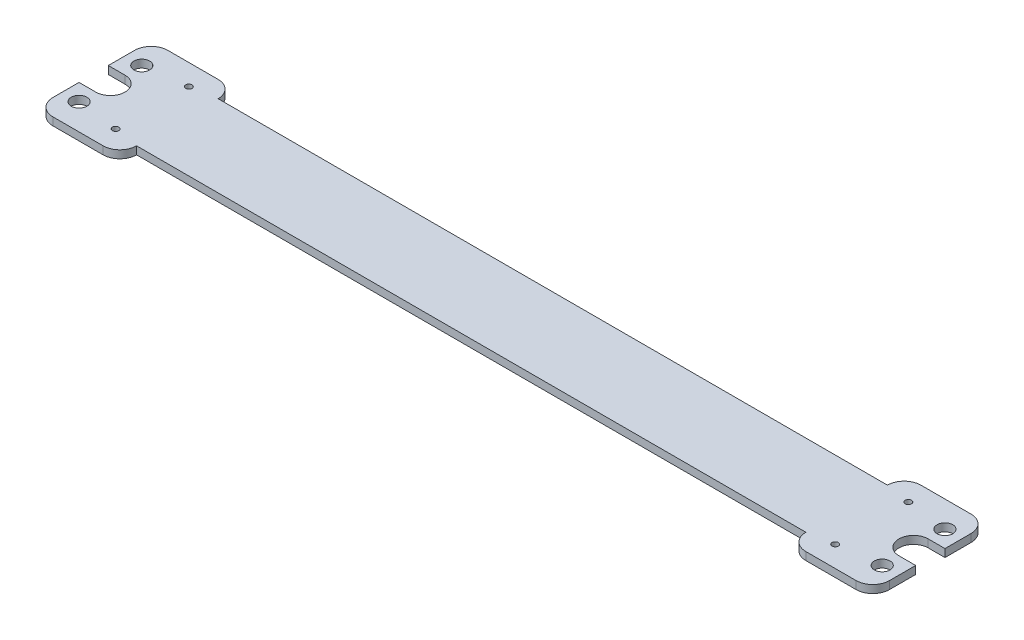
SolidWorks part; units mm, degrees
ref_plane "Front Plane" through (0, 0, 0) normal (0, 0, 1) x (1, 0, 0)
ref_plane "Top Plane" through (0, 0, 0) normal (0, 1, 0) x (1, 0, 0)
ref_plane "Right Plane" through (0, 0, 0) normal (1, 0, 0) x (0, 0, -1)
sketch "Sketch1" plane through (0, 0, 0) normal (0, 1, 0) x (1, 0, 0)
  line L0 (0, -34.925) -> (1.27, -34.925) construction
  line L1 (10.16, 0) -> (40.64, 0)
  line L2 (0, -10.16) -> (0, -26.035)
  line L3 (10.16, -69.85) -> (40.64, -69.85)
  line L5 (10.16, -43.815) -> (0, -43.815)
  line L6 (10.16, -26.035) -> (0, -26.035)
  line L7 (0, -43.815) -> (0, -59.69)
  line L8 (19.05, -34.925) -> (87.4324, -34.925) construction
  line L10 (50.8, -59.69) -> (254, -59.69)
  line L12 (50.8, -10.16) -> (254, -10.16)
  line L13 (254, -59.69) -> (254, -10.16)
  circle A0 centre (10.16, -53.975) radius 4.7625
  circle A1 centre (10.16, -15.875) radius 4.7625
  arc A2 (10.16, -43.815) -> (10.16, -26.035) centre (10.16, -34.925) ccw
  circle A3 centre (10.16, -15.875) radius 6.35 construction
  circle A4 centre (10.16, -53.975) radius 6.35 construction
  arc A5 (0, -59.69) -> (10.16, -69.85) centre (10.16, -59.69) ccw
  arc A6 (10.16, 0) -> (0, -10.16) centre (10.16, -10.16) ccw
  circle A7 centre (35.56, -57.15) radius 1.905
  circle A8 centre (35.56, -12.7) radius 1.905
  arc A9 (40.64, -69.85) -> (50.8, -59.69) centre (40.64, -59.69) ccw
  arc A10 (40.64, 0) -> (50.8, -10.16) centre (40.64, -10.16) cw
  point P22 (0, -69.85)
  point P25 (0, 0)
  point P34 (0, 0)
  point P35 (0, 0)
  point P37 (0, 0)
  point P38 (50.8, -69.85)
  point P40 (0, 0)
  dimension "D3" = 9.525
  dimension "D4" = 9.525
  dimension "D5" = 17.78
  dimension "D10" = 34.925
  dimension "D11" = 12.7
  dimension "D12" = 12.7
  dimension "D13" = 10.16
  dimension "D14" = 3.81
  dimension "D15" = 3.81
  dimension "D22" = 10.16
  dimension "D1" = 69.85
  dimension "D2" = 50.8
  dimension "D6" = 19.05
  dimension "D7" = 19.05
  dimension "D8" = 10.16
  dimension "D9" = 10.16
  dimension "D16" = 12.7
  dimension "D17" = 12.7
  dimension "D18" = 203.2
  dimension "D19" = 49.53
  dimension "D20" = 10.16
  dimension "D21" = 50.8
extrude "Boss-Extrude1" add sketch "Sketch1" along normal blind 4.7625
mirror "Mirror1" about plane through (254, 4.7625, 59.69) normal (-1, 0, 0) of "Boss-Extrude1"
